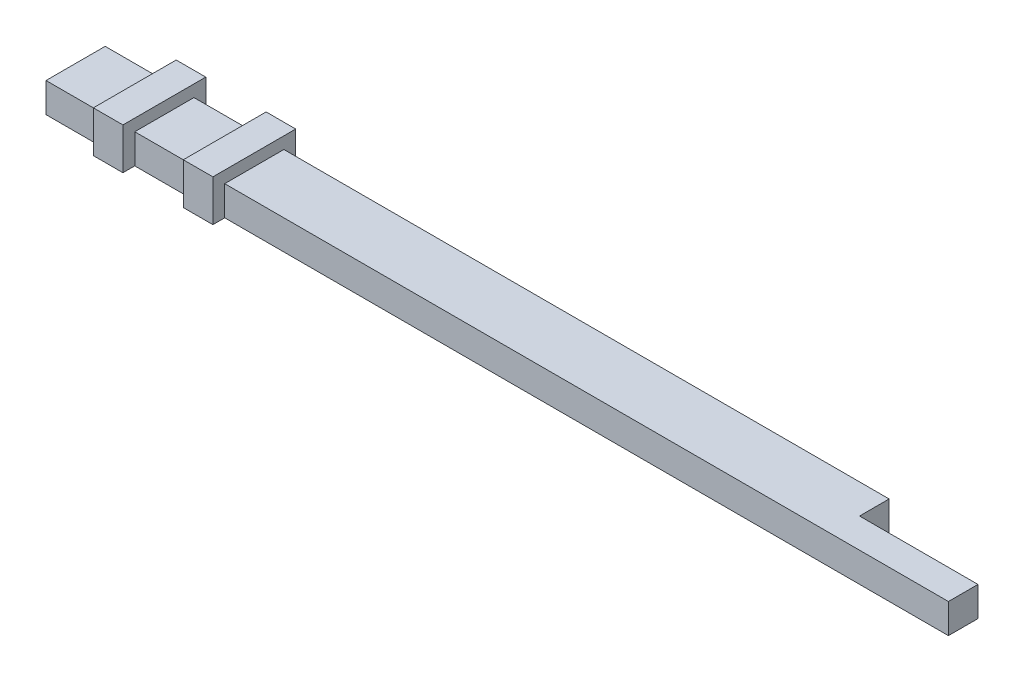
SolidWorks part; units mm, degrees
ref_plane "Front Plane" through (0, 0, 0) normal (0, 0, 1) x (1, 0, 0)
ref_plane "Top Plane" through (0, 0, 0) normal (0, 1, 0) x (1, 0, 0)
ref_plane "Right Plane" through (0, 0, 0) normal (1, 0, 0) x (0, 0, -1)
sketch "Sketch1" plane through (0, 0, 0) normal (0, 1, 0) x (1, 0, 0)
  line L0 (132.4815, 10) -> (132.4815, 5)
  line L1 (0, 0) -> (142.5, 0)
  line L2 (0, 0) -> (0, 10)
  line L3 (0, 10) -> (132.4815, 10)
  line L5 (142.5, 0) -> (152.5, 0)
  line L7 (142.4815, 5) -> (152.5, 5)
  line L8 (152.5, 0) -> (152.5, 5)
  line L9 (132.4815, 5) -> (142.4815, 5)
  dimension "D1" = 142.5
  dimension "D2" = 10
  dimension "D3" = 10
  dimension "D4" = 10
extrude "Boss-Extrude1" add sketch "Sketch1" along normal blind 5
ref_plane "Plane1" through (10, 0, 0) normal (-1, 0, 0) x (0, 0, 1)
sketch "Sketch2" plane through (10, 0, 0) normal (-1, 0, 0) x (0, 0, 1)
  line L0 (-10, 5) -> (0, 5) construction
  line L1 (-12, 7) -> (2, 7)
  line L2 (-12, 7) -> (-12, 0)
  line L3 (-12, 0) -> (2, 0)
  line L4 (2, 7) -> (2, 0)
  line L5 (-10, 0) -> (0, 0) construction
  line L6 (0, 5) -> (0, 0) construction
  line L7 (-10, 5) -> (-10, 0) construction
  dimension "D1" = 2
  dimension "D2" = 0
  dimension "D3" = 2
  dimension "D4" = 2
extrude "Boss-Extrude2" add sketch "Sketch2" against normal blind 5
ref_plane "Plane2" through (30.2, 0, 0) normal (1, 0, 0) x (0, 0, -1)
sketch "Sketch3" plane through (30.2, 0, 0) normal (1, 0, 0) x (0, 0, -1)
  line L1 (-2, 7) -> (12, 7)
  line L2 (-2, 7) -> (-2, 0)
  line L3 (-2, 0) -> (12, 0)
  line L4 (12, 7) -> (12, 0)
extrude "Boss-Extrude3" add sketch "Sketch3" against normal blind 5
